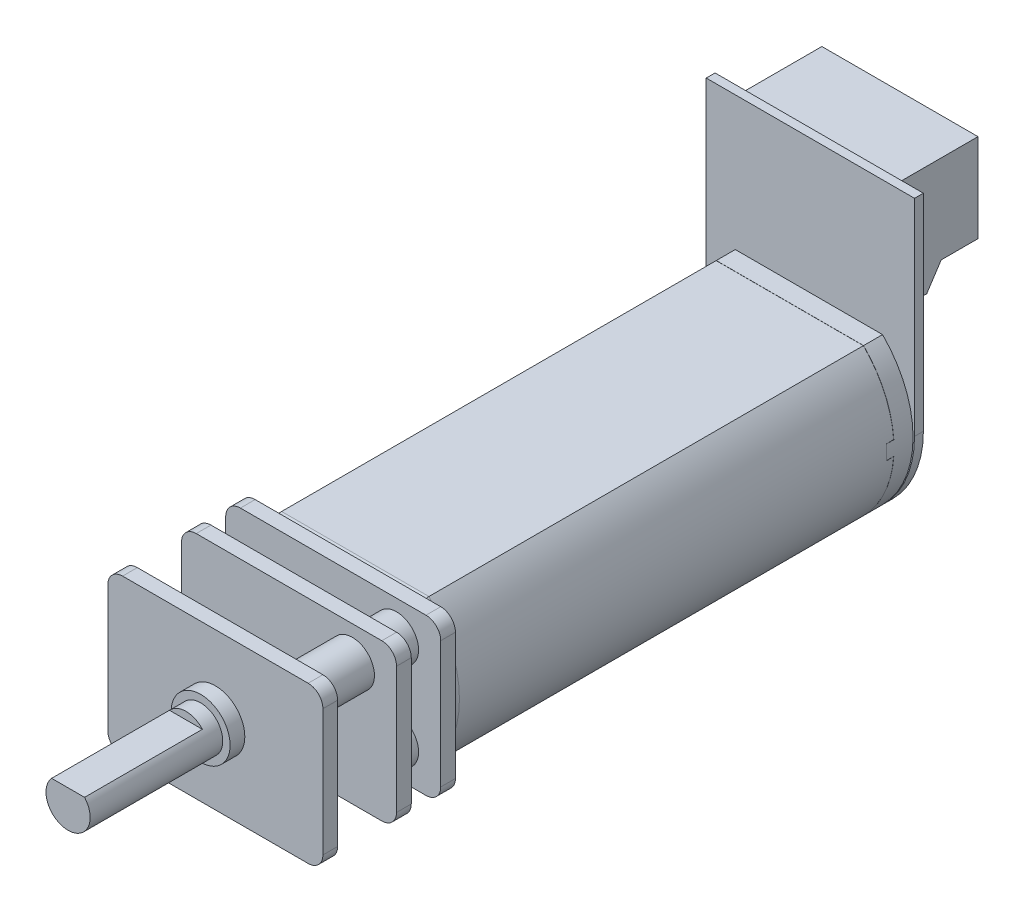
SolidWorks part; units mm, degrees
ref_plane "Front Plane" through (0, 0, 0) normal (0, 0, 1) x (1, 0, 0)
ref_plane "Top Plane" through (0, 0, 0) normal (0, 1, 0) x (1, 0, 0)
ref_plane "Right Plane" through (0, 0, 0) normal (1, 0, 0) x (0, 0, -1)
sketch "Sketch1" plane through (0, 0, 0) normal (0, 0, 1) x (1, 0, 0)
  line L1 (-5, 5) -> (5, 5)
  line L3 (-5, -5) -> (5, -5)
  line L5 (-5, 5) -> (5, -5) construction
  line L6 (-5, -5) -> (5, 5) construction
  arc A0 (-5, 5) -> (-5, -5) centre (0, 0) ccw
  arc A1 (5, -5) -> (5, 5) centre (0, 0) ccw
  dimension "D2" = 10
  dimension "D1" = 10
extrude "Boss-Extrude1" add sketch "Sketch1" along normal mid plane 30
fillet "Fillet1" radius 0.5 4 edges at (-7.0711, 0, 15) (0, -5, 15) (7.0711, 0, 15) (0, 5, 15)
sketch "Sketch2" plane through (0, 0, 0) normal (1, 0, 0) x (0, 0, -1)
  line L0 (15, -5) -> (15, 5) construction
  line L1 (14.5, 0.5) -> (15.5, 0.5)
  line L2 (14.5, 0.5) -> (14.5, -0.5)
  line L3 (14.5, -0.5) -> (15.5, -0.5)
  line L4 (15.5, 0.5) -> (15.5, -0.5)
  line L5 (14.5, 0.5) -> (15.5, -0.5) construction
  line L6 (14.5, -0.5) -> (15.5, 0.5) construction
  point P0 (15, 0)
  dimension "D1" = 1
  dimension "D2" = 1
extrude "Cut-Extrude1" cut sketch "Sketch2" against normal mid plane 16
sketch "Sketch3" plane through (0, 0, 0) normal (1, 0, 0) x (0, 0, -1)
  line L0 (15, 5) -> (15, 0.5) construction
  line L1 (15, 0.5) -> (14.5, 0.5) construction
  line L2 (14.5, 0.5) -> (14.5, -0.5) construction
  line L3 (14.5, -0.5) -> (15, -0.5) construction
  line L4 (15, -0.5) -> (15, -5) construction
  line L5 (15.01, -5) -> (16.3, -5)
  line L6 (16.3, -5) -> (16.3, 5)
  line L7 (16.3, 5) -> (15.01, 5)
  line L8 (15.01, 5) -> (15.01, 0.49)
  line L9 (15.01, 0.49) -> (14.51, 0.49)
  line L10 (14.51, 0.49) -> (14.51, -0.49)
  line L11 (14.51, -0.49) -> (15.01, -0.49)
  line L12 (15.01, -0.49) -> (15.01, -5)
  dimension "D1" = 1.3
  dimension "D2" = 0.01
extrude "Boss-Extrude2" add sketch "Sketch3" along normal up to surface and the other way up to surface up to face at (6.3894, 0, -7.5) other way up to face at (-6.3894, 0, -7.5)
sketch "Sketch4" plane through (0, 0, -16.3) normal (0, 0, -1) x (-1, 0, 0)
  line L1 (-0.5, 0.5) -> (0.5, 0.5)
  line L2 (-0.5, 0.5) -> (-0.5, -0.5)
  line L3 (-0.5, -0.5) -> (0.5, -0.5)
  line L4 (0.5, 0.5) -> (0.5, -0.5)
  line L5 (-0.5, 0.5) -> (0.5, -0.5) construction
  line L6 (-0.5, -0.5) -> (0.5, 0.5) construction
  point P0 (0, 0)
  dimension "D1" = 1
  dimension "D2" = 1
extrude "Boss-Extrude3" add sketch "Sketch4" along normal blind 1
ref_plane "Plane1" through (0, 0, -16.4) normal (0, 0, -1) x (-1, 0, 0)
sketch "Sketch5" plane through (0, 0, -16.4) normal (0, 0, -1) x (-1, 0, 0)
  line L0 (-5, -5) -> (5, -5)
  line L1 (-7.0711, 0) -> (7.0711, 0) construction
  line L2 (-7.0711, 0) -> (-7.0711, 14)
  line L3 (-7.0711, 14) -> (7.0711, 14)
  line L4 (7.0711, 14) -> (7.0711, 0)
  arc A0 (-7.0711, 0) -> (-5, -5) centre (0, 0) ccw
  arc A1 (5, -5) -> (7.0711, 0) centre (0, 0) ccw
  dimension "D1" = 19
extrude "Boss-Extrude4" add sketch "Sketch5" along normal blind 0.6
sketch "Sketch6" plane through (0, 0, 0) normal (1, 0, 0) x (0, 0, -1)
  line L0 (17, 13.7) -> (22.48, 13.7)
  line L1 (17, 14) -> (17, 0) construction
  line L2 (22.48, 13.7) -> (22.48, 7.7)
  line L3 (22.48, 7.7) -> (19.98, 7.7)
  line L4 (19.98, 7.7) -> (19, 6.2)
  line L5 (19, 6.2) -> (17, 6.2)
  line L6 (17, 6.2) -> (17, 13.7)
  line L7 (17, 14) -> (16.4, 14) construction
  dimension "D1" = 5.48
  dimension "D2" = 6
  dimension "D3" = 0.3
  dimension "D4" = 1.5
  dimension "D5" = 2
  dimension "D6" = 2.5
extrude "Boss-Extrude5" add sketch "Sketch6" along normal mid plane 10.6
shell "Shell1" thickness 0.7 removed face at (0, 10.7, -22.48)
sketch "Sketch7" plane through (0, 0, 15) normal (0, 0, 1) x (1, 0, 0)
  line L0 (-5, 5) -> (5, 5) construction
  line L1 (-6.3, 5.3) -> (6.3, 5.3)
  line L2 (-7.3, 4.3) -> (-7.3, -4.3)
  line L3 (-6.3, -5.3) -> (6.3, -5.3)
  line L4 (7.3, 4.3) -> (7.3, -4.3)
  line L5 (-7.3, 5.3) -> (7.3, -5.3) construction
  line L6 (-7.3, -5.3) -> (7.3, 5.3) construction
  arc A0 (-5, 5) -> (-5, -5) centre (0, 0) ccw construction
  arc A1 (-7.3, -4.3) -> (-6.3, -5.3) centre (-6.3, -4.3) ccw
  arc A2 (6.3, -5.3) -> (7.3, -4.3) centre (6.3, -4.3) ccw
  arc A3 (6.3, 5.3) -> (7.3, 4.3) centre (6.3, 4.3) cw
  arc A4 (-6.3, 5.3) -> (-7.3, 4.3) centre (-6.3, 4.3) ccw
  point P0 (0, 0)
  dimension "D3" = 1
  dimension "D1" = 0.3
  dimension "D2" = 7.3
extrude "Boss-Extrude6" add sketch "Sketch7" along normal blind 1
sketch "Sketch8" plane through (0, 0, 16) normal (0, 0, 1) x (1, 0, 0)
  line L0 (4.3, -5.3) -> (4.3, 5.3) construction
  line L1 (-6.3, -5.3) -> (6.3, -5.3) construction
  line L2 (6.3, 5.3) -> (-6.3, 5.3) construction
  line L3 (7.3, -4.3) -> (7.3, 4.3) construction
  line L4 (-7.3, 4.3) -> (-7.3, -4.3) construction
  circle A0 centre (4.3, 3) radius 1.5
  circle A1 centre (4.3, -3) radius 1.5
  circle A2 centre (-4.3, -3) radius 1.5
  dimension "D2" = 3
  dimension "D6" = 3
  dimension "D1" = 3
  dimension "D3" = 2.3
  dimension "D4" = 2.3
  dimension "D5" = 3
  dimension "D7" = 2.3
extrude "Boss-Extrude7" add sketch "Sketch8" along normal blind 2
sketch "Sketch10" plane through (0, 0, 18) normal (0, 0, 1) x (1, 0, 0)
  line L30 (7.3, -4.3) -> (7.3, 4.3)
  line L31 (-6.3, -5.3) -> (6.3, -5.3)
  line L32 (-7.3, 4.3) -> (-7.3, -4.3)
  line L33 (6.3, 5.3) -> (-6.3, 5.3)
  line L34 (7.3, -4.3) -> (7.3, 4.3)
  line L35 (-6.3, -5.3) -> (6.3, -5.3)
  line L36 (-7.3, 4.3) -> (-7.3, -4.3)
  line L37 (6.3, 5.3) -> (-6.3, 5.3)
  arc A15 (-6.3, 5.3) -> (-7.3, 4.3) centre (-6.3, 4.3) ccw
  arc A16 (-7.3, -4.3) -> (-6.3, -5.3) centre (-6.3, -4.3) ccw
  arc A17 (6.3, -5.3) -> (7.3, -4.3) centre (6.3, -4.3) ccw
  arc A18 (7.3, 4.3) -> (6.3, 5.3) centre (6.3, 4.3) ccw
  arc A19 (-6.3, 5.3) -> (-7.3, 4.3) centre (-6.3, 4.3) ccw
  arc A20 (-7.3, -4.3) -> (-6.3, -5.3) centre (-6.3, -4.3) ccw
  arc A21 (6.3, -5.3) -> (7.3, -4.3) centre (6.3, -4.3) ccw
  arc A22 (7.3, 4.3) -> (6.3, 5.3) centre (6.3, 4.3) ccw
  dimension "D1" = 0
extrude "Boss-Extrude8" add sketch "Sketch10" along normal blind 1
sketch "Sketch12" plane through (0, 0, 19) normal (0, 0, 1) x (1, 0, 0)
  circle A5 centre (-4.3, -3) radius 1.5
  circle A6 centre (-4.3, -3) radius 1.5
  circle A8 centre (4.3, 3) radius 1.5
  circle A9 centre (4.3, 3) radius 1.5
  dimension "D1" = 0
  dimension "D2" = 0
extrude "Boss-Extrude9" add sketch "Sketch12" along normal blind 4
sketch "Sketch13" plane through (0, 0, 23) normal (0, 0, 1) x (1, 0, 0)
  line L8 (6.3, 5.3) -> (-6.3, 5.3)
  line L9 (-7.3, 4.3) -> (-7.3, -4.3)
  line L10 (-6.3, -5.3) -> (6.3, -5.3)
  line L11 (7.3, -4.3) -> (7.3, 4.3)
  line L12 (6.3, 5.3) -> (-6.3, 5.3)
  line L13 (-7.3, 4.3) -> (-7.3, -4.3)
  line L14 (-6.3, -5.3) -> (6.3, -5.3)
  line L15 (7.3, -4.3) -> (7.3, 4.3)
  arc A8 (7.3, 4.3) -> (6.3, 5.3) centre (6.3, 4.3) ccw
  arc A9 (-6.3, 5.3) -> (-7.3, 4.3) centre (-6.3, 4.3) ccw
  arc A10 (-7.3, -4.3) -> (-6.3, -5.3) centre (-6.3, -4.3) ccw
  arc A11 (6.3, -5.3) -> (7.3, -4.3) centre (6.3, -4.3) ccw
  arc A12 (7.3, 4.3) -> (6.3, 5.3) centre (6.3, 4.3) ccw
  arc A13 (-6.3, 5.3) -> (-7.3, 4.3) centre (-6.3, 4.3) ccw
  arc A14 (-7.3, -4.3) -> (-6.3, -5.3) centre (-6.3, -4.3) ccw
  arc A15 (6.3, -5.3) -> (7.3, -4.3) centre (6.3, -4.3) ccw
  dimension "D1" = 0
extrude "Boss-Extrude10" add sketch "Sketch13" along normal blind 1
sketch "Sketch14" plane through (0, 0, 24) normal (0, 0, 1) x (1, 0, 0)
  circle A0 centre (0, 0) radius 1.5
  dimension "D1" = 3
extrude "Cut-Extrude2" cut sketch "Sketch14" against normal blind 1
sketch "Sketch15" plane through (0, 0, 24) normal (0, 0, 1) x (1, 0, 0)
  circle A1 centre (0, 0) radius 2
  circle A2 centre (0, 0) radius 1.5
  circle A3 centre (0, 0) radius 1.5
  dimension "D2" = 4
  dimension "D1" = 0
extrude "Boss-Extrude11" add sketch "Sketch15" along normal blind 1
sketch "Sketch16" plane through (0, 0, 23) normal (0, 0, -1) x (-1, 0, 0)
  circle A2 centre (0, 0) radius 1.5
  circle A3 centre (0, 0) radius 1.5
  dimension "D1" = 0
extrude "Boss-Extrude12" add sketch "Sketch16" against normal blind 11
sketch "Sketch17" plane through (0, 0, 34) normal (0, 0, 1) x (1, 0, 0)
  line L0 (0, 1.5) -> (0, -1.5) construction
  line L1 (-2.393, 1) -> (2.3621, 1)
  line L2 (-2.393, 1) -> (-2.393, 3)
  line L3 (-2.393, 3) -> (2.3621, 3)
  line L4 (2.3621, 1) -> (2.3621, 3)
  circle A0 centre (0, 0) radius 1.5 construction
  circle A1 centre (0, 0) radius 1.5 construction
  dimension "D1" = 2.5
extrude "Cut-Extrude3" cut sketch "Sketch17" against normal blind 8
